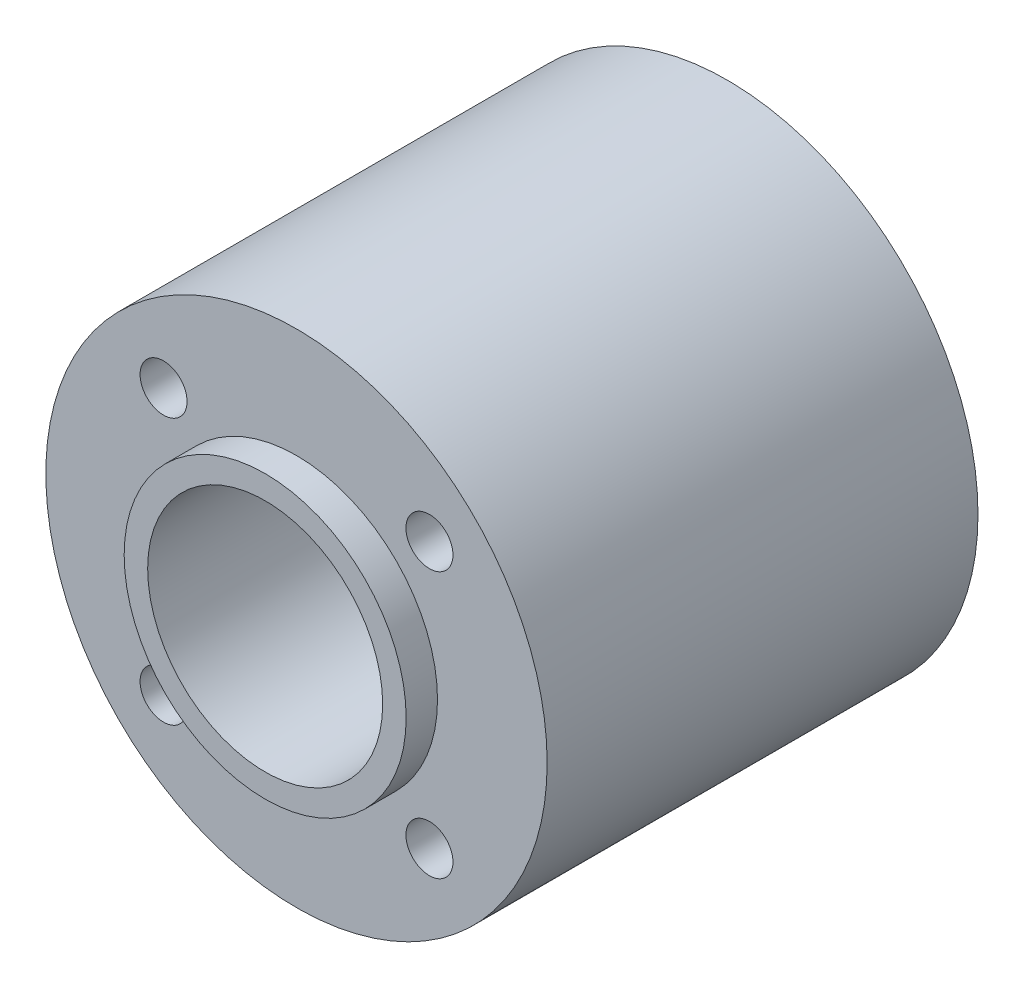
SolidWorks part; units mm, degrees
ref_plane "Front Plane" through (0, 0, 0) normal (0, 0, 1) x (1, 0, 0)
ref_plane "Top Plane" through (0, 0, 0) normal (0, 1, 0) x (1, 0, 0)
ref_plane "Right Plane" through (0, 0, 0) normal (1, 0, 0) x (0, 0, -1)
sketch "Sketch1" plane through (0, 0, 0) normal (0, 0, 1) x (1, 0, 0)
  circle A0 centre (0, 0) radius 16
  circle A1 centre (0, 0) radius 9
  circle A2 centre (0, 0) radius 7.5
  dimension "D1" = 32
  dimension "D2" = 18
  dimension "D3" = 15
extrude "Boss-Extrude1" add sketch "Sketch1" against normal blind 27.5 contours A0 A1 | A1 A2 region at (-15.5475, 0, 0) region at (-8.7454, 0, 0)
extrude "Boss-Extrude2" add sketch "Sketch1<4>" along normal blind 2 contours A1 A2 region at (-8.7454, 0, 0)
sketch "Sketch1<4>" plane through (0, 0, 0) normal (0, 0, 1) x (1, 0, 0) same geometry as "Sketch1"
extrude "Boss-Extrude3" add sketch "Sketch1<5>" against normal blind 2 from surface contours A1 A2 region at (-8.7454, 0, 0) starting at face at (16, 0, -27.5)
sketch "Sketch1<5>" plane through (0, 0, 0) normal (0, 0, 1) x (1, 0, 0) same geometry as "Sketch1"
sketch "Sketch2" plane through (0, 0, 0) normal (0, 0, 1) x (1, 0, 0)
  line L0 (0, 0) -> (-8.4853, 8.4853) construction
  line L1 (0, 0) -> (0, 12) construction
  circle A0 centre (0, 0) radius 12 construction
  circle A1 centre (-8.4853, 8.4853) radius 1.5
  circle A2 centre (8.4853, 8.4853) radius 1.5
  circle A3 centre (8.4853, -8.4853) radius 1.5
  circle A4 centre (-8.4853, -8.4853) radius 1.5
  circle A5 centre (0, 0) radius 9 construction
  point P15 (0, 0)
  dimension "D2" = 24
  dimension "D3" = 3
  dimension "D1" = 45
  dimension "D5" = 8.4853
  dimension "D4" = 4
extrude "Cut-Extrude1" cut sketch "Sketch2" against normal through all
